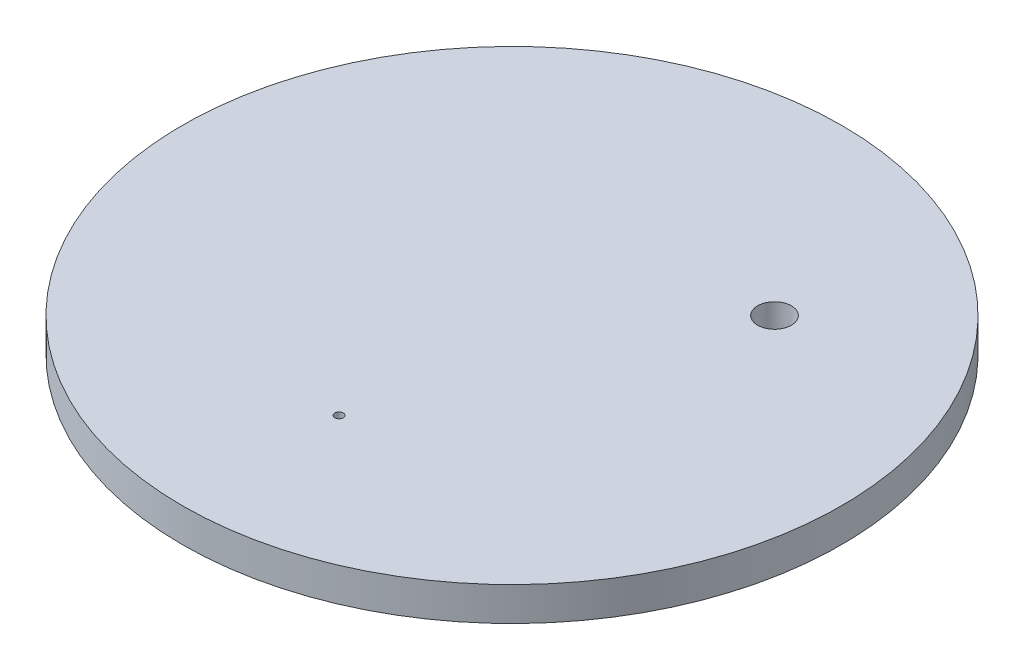
SolidWorks part; units mm, degrees
material "1060 Alloy"
ref_plane "Front Plane" through (0, 0, 0) normal (0, 0, 1) x (1, 0, 0)
ref_plane "Top Plane" through (0, 0, 0) normal (0, 1, 0) x (1, 0, 0)
ref_plane "Right Plane" through (0, 0, 0) normal (1, 0, 0) x (0, 0, -1)
sketch "Sketch1" plane through (0, 0, 0) normal (0, 1, 0) x (1, 0, 0)
  circle A0 centre (0, 0) radius 19.53
  dimension "D1" = 39.06
extrude "Boss-Extrude1" add sketch "Sketch1" along normal blind 1
sketch "Sketch6" plane through (0, 0, 0) normal (0, -1, 0) x (1, 0, 0)
  circle A0 centre (0, 0) radius 19.53
  circle A1 centre (0, 0) radius 9.525
  circle A2 centre (0, 0) radius 19.53 construction
  dimension "D1" = 0
  dimension "D2" = 19.05
extrude "Boss-Extrude3" add sketch "Sketch6" along normal blind 1
thread "Thread1" pitch 0.25 method cut profile "Thread Profile1" start angle 0, offset 0, length 1, pitch 0.25, diameter 19.05
ref_plane "Plane1" through (9.525, -1, 0) normal (0, 0, 1) x (1, 0, 0)
sketch "Thread Profile1" plane through (9.525, -1, 0) normal (0, 0, 1) x (1, 0, 0)
  line L0 (0, 0) -> (0, 0.25) construction
  line L1 (0, 0) -> (0.1353, 0.0781)
  line L2 (0.1353, 0.0781) -> (0.1353, 0.1094)
  line L3 (0.1353, 0.1094) -> (0, 0.1875)
  line L4 (0.1353, 0.0937) -> (0, 0.0937) construction
  line L11 (0, 0) -> (0, 0.1875)
  point P2 (0, 0)
  dimension "Pitch" = 0.25
  dimension "Profile_Angle" = 60
  dimension "Profile_Land" = 0.0312
  dimension "Profile_Height" = 0.1353
sketch "Sketch7" plane through (0, 1, 0) normal (0, 1, 0) x (1, 0, 0)
  circle A0 centre (0, -10.25) radius 0.25
  circle A1 centre (0, 0) radius 9.8
  dimension "D1" = 0.5
  dimension "D2" = 10.25
  dimension "D3" = 19.6
extrude "Cut-Extrude1" cut sketch "Sketch7" against normal through all both and the other way through all contours A1 A0 region at (0, 1, 10.25)
sketch "Sketch8" plane through (0, 1, 0) normal (0, 1, 0) x (1, 0, 0)
  line L0 (0, 0) -> (13.2071, 13.2071) construction
  circle A0 centre (7.7782, 7.7782) radius 1
  dimension "D1" = 2
  dimension "D2" = 11
extrude "Cut-Extrude2" cut sketch "Sketch8" against normal through all both and the other way through all
